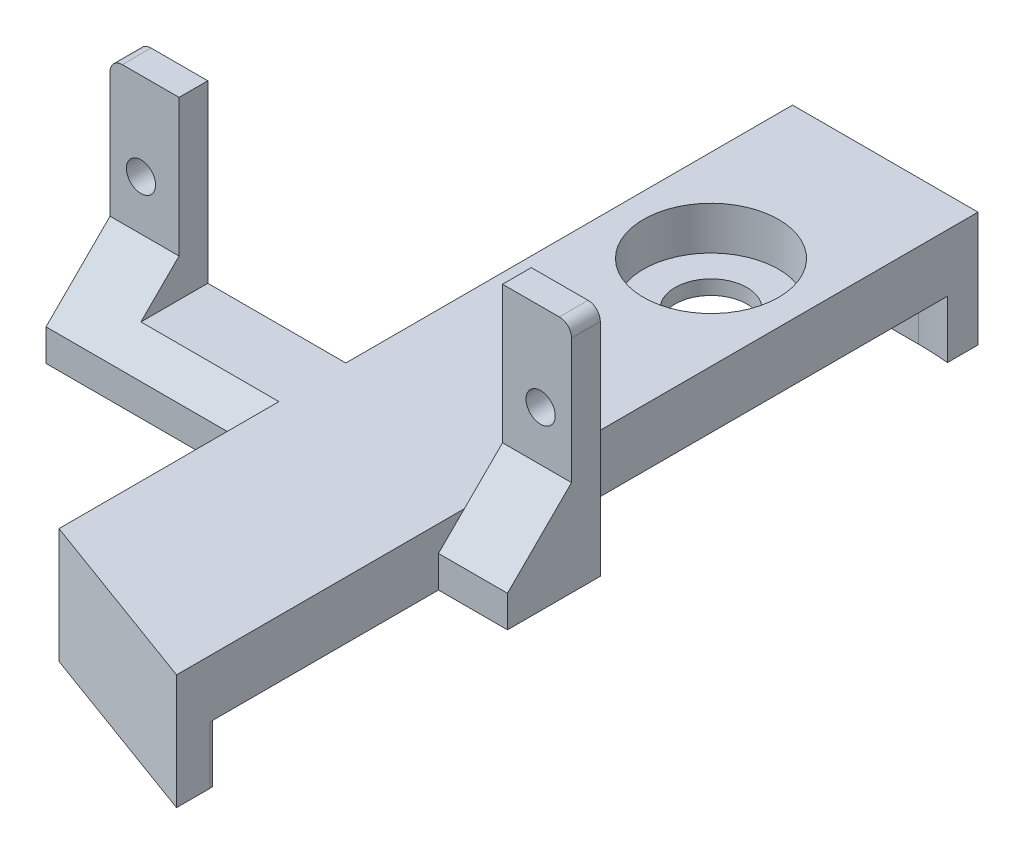
SolidWorks part; units mm, degrees
note: The reader was unsure of these and kept them because the rebuilt part matched: shared geometry of "Sketch2<3>".
ref_plane "Front Plane" through (0, 0, 0) normal (0, 0, 1) x (1, 0, 0)
ref_plane "Top Plane" through (0, 0, 0) normal (0, 1, 0) x (1, 0, 0)
ref_plane "Right Plane" through (0, 0, 0) normal (1, 0, 0) x (0, 0, -1)
sketch "Sketch1" plane through (0, 0, 0) normal (0, 0, 1) x (1, 0, 0)
  line L0 (11.25, -6.1) -> (15.2, -6.1)
  line L1 (11.25, -6.1) -> (11.25, 6.0941)
  line L2 (11.25, 6.0941) -> (15.2, 6.1)
  line L3 (15.2, -6.1) -> (-15.2, -6.1) construction
  line L4 (-10.5, 6.1) -> (-15.2, 6.1) construction
  line L5 (-16.05, 5.25) -> (-16.05, -5.25) construction
  line L6 (-16.05, -5.25) -> (-16.05, -0.55) construction
  line L9 (15.2, -6.1) -> (11.25, -6.1)
  line L10 (-11.25, 6.1) -> (-15.2, 6.1)
  line L11 (-16.05, 5.25) -> (-16.05, -5.25)
  line L12 (-16.05, -5.25) -> (-16.05, -0.55)
  line L13 (16.05, 5.25) -> (16.05, -5.25)
  line L14 (-15.2, -6.1) -> (-16.05, -6.1)
  line L15 (-11.25, 6.1) -> (-11.25, -6.1)
  line L16 (-11.25, -5.25) -> (-11.25, 5.25) construction
  line L17 (-11.25, -5.25) -> (-11.25, 5.25) construction
  line L18 (-15.2, 6.1) -> (15.2, 6.1) construction
  line L19 (-11.25, -6.1) -> (-15.2, -6.1)
  line L20 (-16.05, -5.25) -> (-16.05, -6.1)
  line L21 (15.2, -6.1) -> (16.05, -6.1)
  line L22 (16.05, -5.25) -> (16.05, -6.1)
  arc A0 (-15.2, 6.1) -> (-16.05, 5.25) centre (-15.2, 5.25) ccw construction
  arc A1 (-16.05, -5.25) -> (-15.2, -6.1) centre (-15.2, -5.25) ccw construction
  arc A2 (15.2, -6.1) -> (16.05, -5.25) centre (15.2, -5.25) ccw construction
  arc A3 (16.05, 5.25) -> (15.2, 6.1) centre (15.2, 5.25) ccw construction
  arc A4 (-15.2, 6.1) -> (-16.05, 5.25) centre (-15.2, 5.25) ccw
  arc A5 (-16.05, -5.25) -> (-15.2, -6.1) centre (-15.2, -5.25) ccw
  arc A6 (15.2, -6.1) -> (16.05, -5.25) centre (15.2, -5.25) ccw
  arc A7 (16.05, 5.25) -> (15.2, 6.1) centre (15.2, 5.25) ccw
  circle A8 centre (-13.9, 0) radius 1.016
  circle A9 centre (13.9, 0) radius 1.016
  dimension "D1" = 2.032
  dimension "D2" = 2.032
extrude "Boss-Extrude1" add sketch "Sketch1" along normal blind 2 contours L11 A5 L19 L15 L10 A4 A8 | L13 A7 L2 L1 L0 A6 A9 | A6 L21 L22 | A5 L20 L14
sketch "Sketch2" plane through (0, -6.1, 0) normal (0, -1, 0) x (1, 0, 0)
  line L0 (-16.05, 2) -> (16.05, 2)
  line L5 (16.05, 2) -> (16.05, 0)
  line L6 (16.05, 0) -> (-16.05, 0)
  line L7 (-16.05, 0) -> (-16.05, 2)
  line L8 (-1.65, 19.9527) -> (-1.65, -31.0721)
  line L9 (11.25, 2) -> (11.25, 24.6756)
  line L10 (-1.65, -31.0721) -> (11.25, -31.0721)
  line L12 (9.15, -29) -> (4.75, -29) construction
  line L17 (0.9956, 17.9585) -> (38.5044, 33.1523) construction
  line L18 (9.15, -29) -> (4.75, -29)
  line L19 (11.25, 0) -> (11.25, -31.0721)
  line L24 (0.9956, 17.9585) -> (11.25, 22.1123)
  line L26 (0.9768, 18.0049) -> (11.2312, 22.1586)
  line L27 (9.15, -29.05) -> (4.75, -29.05)
  line L28 (11.2312, 22.1586) -> (11.25, 22.3411)
  line L30 (-1.65, 19.9527) -> (11.25, 24.6756)
  circle A1 centre (4.75, -19) radius 4.7
  arc A2 (9.15, -29) -> (19.225, -26.277) centre (9.15, -9) ccw construction
  arc A3 (-5.25, -19) -> (4.75, -29) centre (4.75, -19) ccw construction
  arc A4 (0.9956, 17.9585) -> (-5.25, 8.6901) centre (4.75, 8.6901) ccw construction
  arc A5 (9.15, -29) -> (11.25, -28.8894) centre (9.15, -9) ccw
  arc A10 (-1.65, -26.6837) -> (4.75, -29) centre (4.75, -19) ccw
  arc A12 (0.9956, 17.9585) -> (-1.65, 16.3738) centre (4.75, 8.6901) ccw
  arc A13 (0.9768, 18.0049) -> (-1.65, 16.4388) centre (4.75, 8.6901) ccw
  arc A14 (9.15, -29.05) -> (11.25, -28.9397) centre (9.15, -9) ccw
  arc A15 (-1.65, -26.7487) -> (4.75, -29.05) centre (4.75, -19) ccw
  arc A16 (0.9768, 18.0049) -> (-1.682, 16.4122) centre (4.75, 8.6901) ccw construction
  arc A18 (-1.682, -26.7222) -> (4.75, -29.05) centre (4.75, -19) ccw construction
  arc A19 (9.15, -29.05) -> (11.2553, -28.9392) centre (9.15, -9) ccw construction
  point P28 (-6.5991, -18.7771)
  point P29 (-19.7755, -35.4742)
  point P30 (3.3836, -37.5589)
  point P31 (14.7015, -26.7317)
  point P32 (3.6798, -24.3792)
  point P33 (-7.2167, -27.2566)
  point P38 (4.75, -29.2)
  point P39 (12.8214, 0)
  point P40 (11.38, -26.7513)
  point P43 (12.8214, 6.5789)
  point P44 (-80.0361, -11.1071)
  point P45 (-172.8435, 6.8395)
  point P46 (-2.7186, 49.3707)
  point P47 (-2.7186, 0)
  point P50 (8.579, 18.1441)
  point P51 (5.0465, 9.2885)
  point P52 (11.3686, 16.4251)
  dimension "D3" = 6.4
  dimension "D6" = 9.4
  dimension "D1" = 11.3
  dimension "D4" = 6.5
  dimension "D5" = 0.05
extrude "Boss-Extrude2" add sketch "Sketch2" along normal blind 3
extrude "Boss-Extrude5" add sketch "Sketch2<3>" along normal blind 8
sketch "Sketch2<3>" plane through (0, -6.1, 0) normal (0, -1, 0) x (1, 0, 0) same geometry as "Sketch2"
sketch "Sketch3" plane through (11.25, 0, 0) normal (1, 0, 0) x (0, 0, -1)
  line L0 (-7.6658, -9.1) -> (-2, -3.4575)
  line L1 (-2, -9.1) -> (-22.3411, -9.1) construction
  line L2 (-2, -9.1) -> (-2, 5.25) construction
  line L3 (-2, -3.4575) -> (-2, -9.1)
  line L4 (-2, -9.1) -> (-7.6658, -9.1)
  line L5 (-2, -6.1) -> (-2, 6.0941) construction
extrude "Boss-Extrude6" add sketch "Sketch3" along normal up to surface and the other way up to surface up to face at (16.05, -1.925, 1) other way up to face at (-16.05, -1.925, 1)
sketch "Sketch4" plane through (0, -6.1, 0) normal (0, 1, 0) x (1, 0, 0)
  line L0 (-11.25, 0) -> (-11.25, -14.1277)
  line L1 (-11.25, -14.1277) -> (11.25, -14.1277)
  line L2 (11.25, -4.6534) -> (11.25, -24.6756) construction
  line L3 (11.25, -14.1277) -> (11.25, 0)
  line L4 (11.25, 0) -> (-11.25, 0)
extrude "Cut-Extrude1" cut sketch "Sketch4" along normal blind 7
fillet "Fillet1" radius 0.5 2 edges at (-8.85, -9.1, 7.6658) (13.65, -9.1, 7.6658)
sketch "Sketch5" plane through (0, -9.1, 0) normal (0, -1, 0) x (1, 0, 0)
  line L3 (-1.65, 16.4388) -> (-1.65, 6.4552)
  line L14 (4.75, -29.05) -> (9.15, -29.05)
  line L15 (-1.65, 16.4388) -> (-1.65, 6.4552)
  line L16 (-16.05, 0) -> (-1.65, 0)
  line L17 (-1.65, 6.4552) -> (-16.05, 6.4552)
  line L18 (-1.65, 6.4552) -> (-16.05, 6.4552)
  line L19 (-16.05, 6.4552) -> (-16.05, 0)
  line L20 (-16.05, 6.4552) -> (-16.05, 0)
  line L21 (16.05, 0) -> (16.05, 6.4552)
  line L22 (-1.65, 0) -> (-1.65, -26.7487)
  line L23 (-1.65, 0) -> (-1.65, -26.7487)
  line L24 (4.75, -29.05) -> (9.15, -29.05)
  line L29 (-16.05, 0) -> (-1.65, 0)
  line L34 (16.05, 0) -> (16.05, 6.4552)
  line L39 (11.25, -28.9397) -> (11.25, 0)
  line L40 (11.25, -28.9397) -> (11.25, 0)
  line L41 (11.25, 0) -> (16.05, 0)
  line L42 (11.25, 0) -> (16.05, 0)
  line L43 (16.05, 6.4552) -> (11.25, 6.4552)
  line L44 (16.05, 6.4552) -> (11.25, 6.4552)
  line L45 (11.25, 6.4552) -> (11.25, 22.3411)
  line L46 (11.25, 6.4552) -> (11.25, 22.3411)
  line L57 (11.25, 22.3411) -> (11.2312, 22.1586)
  line L58 (11.25, 22.3411) -> (11.2312, 22.1586)
  line L59 (11.2312, 22.1586) -> (0.9768, 18.0049)
  line L60 (11.2312, 22.1586) -> (0.9768, 18.0049)
  circle A0 centre (4.75, -19) radius 2.5
  arc A2 (-1.65, -26.7487) -> (4.75, -29.05) centre (4.75, -19) ccw
  arc A15 (-1.65, -26.7487) -> (4.75, -29.05) centre (4.75, -19) ccw
  arc A18 (9.15, -29.05) -> (11.25, -28.9397) centre (9.15, -9) ccw
  arc A20 (9.15, -29.05) -> (11.25, -28.9397) centre (9.15, -9) ccw
  arc A21 (0.9768, 18.0049) -> (-1.65, 16.4388) centre (4.75, 8.6901) ccw
  arc A22 (0.9768, 18.0049) -> (-1.65, 16.4388) centre (4.75, 8.6901) ccw
  dimension "D1" = 5
  dimension "D2" = 0
extrude "Boss-Extrude7" add sketch "Sketch5" along normal blind 1
sketch "Sketch6" plane through (0, 0, 6.4552) normal (0, 0, 1) x (1, 0, 0)
  line L1 (11.25, -10.1) -> (16.5637, -10.1)
  line L2 (11.25, -10.1) -> (11.25, -5.5007)
  line L3 (11.25, -5.5007) -> (16.5637, -5.5007)
  line L4 (16.5637, -10.1) -> (16.5637, -5.5007)
  line L5 (-1.65, -10.1) -> (-17.8132, -10.1)
  line L6 (-1.65, -10.1) -> (-1.65, -4.7554)
  line L7 (-1.65, -4.7554) -> (-17.8132, -4.7554)
  line L8 (-17.8132, -10.1) -> (-17.8132, -4.7554)
extrude "Cut-Extrude2" cut sketch "Sketch6" along normal blind 5
